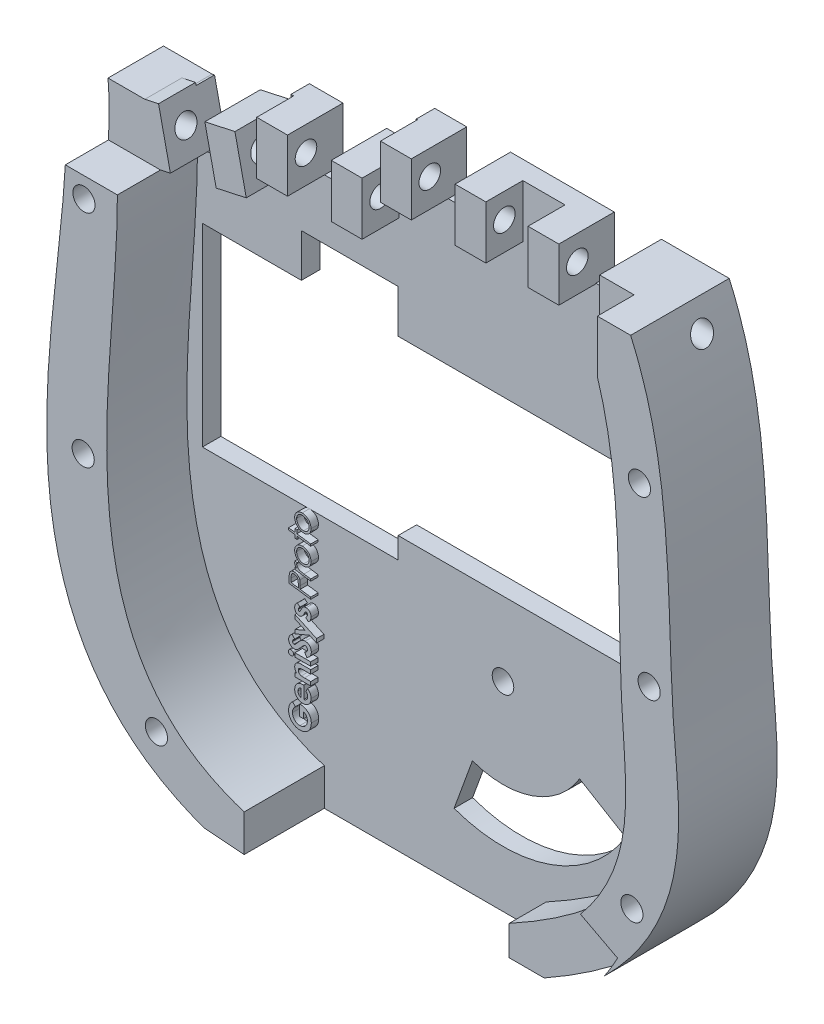
SolidWorks part; units mm, degrees
ref_plane "Front Plane" through (0, 0, 0) normal (0, 0, 1) x (1, 0, 0)
ref_plane "Top Plane" through (0, 0, 0) normal (0, 1, 0) x (1, 0, 0)
ref_plane "Right Plane" through (0, 0, 0) normal (1, 0, 0) x (0, 0, -1)
sketch "Sketch2" plane through (0, 0, 0) normal (0, 0, 1) x (1, 0, 0)
  line L0 (-18, 0) -> (18, 0)
  line L1 (-18, 0) -> (-18, 6)
  line L2 (18, 4.8369) -> (18, 0)
  line L3 (35.71, 104.3369) -> (-3.08, 104.3369)
  line L4 (-3.08, 104.3369) -> (-5.4197, 97.6369)
  line L5 (-5.4197, 97.6369) -> (-23.4197, 97.6369)
  line L6 (-23.4197, 97.6369) -> (-23.3737, 94.5493)
  line L7 (-23.3737, 94.5493) -> (-39.2, 91.09)
  spline S0 degree 3 poles (-18, 6) (-53.1212, 16.9957) (-35.2084, 66.9995) (-39.2, 91.09) knots 0 0 0 0 1 1 1 1
  spline S1 degree 3 poles (18, 4.8369) (37.3806, 15.4098) (45.3229, 29.9302) (41.68, 63.651) (44.3193, 88.8574) (35.71, 104.3369) knots 0 0 0 0 0.323626 0.459678 1 1 1 1
  dimension "D1" = 18
  dimension "D2" = 18
  dimension "D3" = 6
  dimension "D4" = 10.5
  dimension "D5" = 34.2
  dimension "D6" = 40.39
  dimension "D7" = 29.82
  dimension "D8" = 17.22
  dimension "D9" = 52.46
  dimension "D10" = 21.2
  dimension "D11" = 17.71
  dimension "D12" = 25.6263
  dimension "D13" = 25.26
  dimension "D14" = 38.79
  dimension "D15" = 109.25
  dimension "D16" = 6.7
  dimension "D17" = 18
  dimension "D18" = 16.2
extrude "Boss-Extrude1" add sketch "Sketch2" along normal blind 3
sketch "Sketch19" plane through (0, 0, 3) normal (0, 0, 1) x (1, 0, 0)
  line L0 (-3.953, 101.8369) -> (36.9908, 101.8369) construction
  line L1 (35.71, 104.3369) -> (-3.08, 104.3369) construction
  line L2 (16.315, 104.3369) -> (16.315, 82.7196) construction
  line L3 (-3.08, 104.3369) -> (-5.4197, 97.6369) construction
  line L4 (-5.0007, 98.8369) -> (38.0408, 98.8369) construction
  line L5 (-14.4197, 97.6369) -> (-14.4197, 19.4647) construction
  line L6 (-5.4197, 97.6369) -> (-23.4197, 97.6369) construction
  line L7 (32.86, 95.8369) -> (-25.0798, 95.8369) construction
  line L8 (-25.0798, 92.8369) -> (-5.4479, 92.8369) construction
  line L9 (-31.2868, 92.8197) -> (-30.2191, 87.935) construction
  line L10 (-30.2191, 87.935) -> (-26.5082, 88.7461) construction
  line L11 (-39.2, 91.09) -> (-23.3737, 94.5493) construction
  line L12 (-38.8717, 88.6027) -> (-23.0453, 92.0621) construction
  circle A16 centre (-18.9197, 77.8369) radius 1.6
  circle A17 centre (1.7305, 83.8369) radius 1.6
  circle A18 centre (23.11, 83.8369) radius 1.6
  circle A19 centre (22.9993, 31.1499) radius 1.6
  circle A20 centre (-32.5698, 65.7383) radius 1.6
  circle A21 centre (-32.5698, 43.2412) radius 1.6
  circle A22 centre (0, 14.3798) radius 1.6
  circle A23 centre (38.0408, 78.6285) radius 1.6
  circle A24 centre (38.0408, 56.4962) radius 1.6
  circle A25 centre (0.5343, 43.8548) radius 1.6
  circle A26 centre (-19.1897, 28.8836) radius 1.6
  spline S0 degree 3 poles (18, 4.8369) (37.3806, 15.4098) (45.3229, 29.9302) (41.68, 63.651) (44.3193, 88.8574) (35.71, 104.3369) knots 0 0 0 0 0.323626 0.459678 1 1 1 1 construction
  spline S1 degree 3 poles (-39.2, 91.09) (-35.2084, 66.9995) (-53.1212, 16.9957) (-18, 6) knots 0 0 0 0 1 1 1 1 construction
  dimension "D15" = 3.2
  dimension "D17" = 3.2
  dimension "D19" = 3.2
  dimension "D24" = 3.2
  dimension "D27" = 3.2
  dimension "D28" = 3.2
  dimension "D29" = 3.2
  dimension "D30" = 3.2
  dimension "D31" = 3.2
  dimension "D32" = 3.2
  dimension "D33" = 3.2
  dimension "D34" = 40
  dimension "D1" = 2.5
  dimension "D6" = 3
  dimension "D9" = 3
  dimension "D10" = 2.5
  dimension "D16" = 4.5
  dimension "D21" = 12
  dimension "D22" = 12
sketch "Sketch21" plane through (0, 0, 3) normal (0, 0, 1) x (1, 0, 0)
  line L0 (-19, 10) -> (-19, 40.6454) construction
  line L1 (-18, 6) -> (-18, 0) construction
  line L3 (-18, 0) -> (18, 0) construction
  text T0 "<b>GeniSys</b> <i>Proto</i>"
  dimension "D1" = 1
  dimension "D2" = 10
sketch "Sketch22" plane through (0, 0, 0) normal (0, 0, -1) x (-1, 0, 0)
  line L0 (-35.71, 104.3369) -> (-31.5125, 104.3369) construction
  line L1 (-26.06, 104.3369) -> (-21.06, 104.3369) construction
  line L2 (14.4197, 97.6369) -> (14.4197, 88.3883) construction
  line L3 (5.4197, 97.6369) -> (23.4197, 97.6369) construction
  line L5 (23.3737, 94.5493) -> (39.2, 91.09) construction
  line L6 (31.3845, 92.7983) -> (30.9574, 90.8444)
  line L7 (28.1815, 78.1443) -> (23.2968, 79.212)
  line L8 (23.2968, 79.212) -> (24.0015, 82.4359)
  line L9 (26.4998, 93.866) -> (31.3845, 92.7983)
  line L11 (34.7549, 92.0616) -> (34.3279, 90.1077)
  line L13 (34.4827, 76.767) -> (35.1874, 79.9908)
  line L14 (-26.06, 89.3369) -> (-21.06, 89.3369)
  line L16 (-5.6675, 99.2369) -> (-5.6675, 95.7369) construction
  line L17 (17.9697, 82.6369) -> (22.9697, 82.6369)
  line L18 (10.8697, 97.6369) -> (5.8697, 97.6369)
  line L19 (10.8697, 92.5369) -> (10.8697, 89.0369)
  line L20 (10.8697, 82.6369) -> (5.8697, 82.6369)
  line L21 (5.8697, 97.6369) -> (5.8697, 95.6369)
  line L22 (17.9697, 97.6369) -> (22.9697, 97.6369)
  line L23 (22.9697, 97.6369) -> (22.9697, 95.6369)
  line L24 (17.9697, 97.6369) -> (17.9697, 95.6369)
  line L25 (-26.06, 104.3369) -> (-26.06, 102.3369)
  line L26 (-9.2175, 104.3369) -> (-14.2175, 104.3369)
  line L27 (-9.2175, 104.3369) -> (-9.2175, 102.3369)
  line L28 (-9.2175, 89.3369) -> (-14.2175, 89.3369)
  line L29 (-14.2175, 104.3369) -> (-14.2175, 102.3369)
  line L31 (-28.5125, 104.3369) -> (-28.5125, 102.3369)
  line L33 (-31.5125, 104.3369) -> (-31.5125, 102.3369)
  line L34 (-21.06, 104.3369) -> (-21.06, 102.3369)
  line L35 (-26.06, 104.3369) -> (-21.06, 104.3369)
  line L36 (-2.1175, 89.3369) -> (2.8825, 89.3369)
  line L37 (-2.1175, 104.3369) -> (-2.1175, 102.3369)
  line L38 (2.8825, 104.3369) -> (2.8825, 102.3369)
  line L39 (-2.1175, 104.3369) -> (2.8825, 104.3369)
  line L45 (30.2955, 87.8159) -> (25.4108, 88.8836)
  line L46 (29.5481, 84.3967) -> (24.6634, 85.4643)
  line L47 (28.8861, 81.3682) -> (24.0015, 82.4359)
  line L48 (30.9574, 90.8444) -> (26.0728, 91.9121)
  line L49 (33.6659, 87.0792) -> (32.9185, 83.66)
  line L50 (37.2587, 89.4671) -> (37.6858, 91.421)
  line L51 (32.2566, 80.6315) -> (31.5519, 77.4076)
  line L52 (35.8493, 83.0193) -> (36.5967, 86.4386)
  line L53 (26.0728, 91.9121) -> (26.4998, 93.866)
  line L54 (30.2955, 87.8159) -> (29.5481, 84.3967)
  line L55 (28.8861, 81.3682) -> (28.1815, 78.1443)
  line L56 (24.6634, 85.4643) -> (25.4108, 88.8836)
  line L57 (2.8825, 102.3369) -> (-2.1175, 102.3369)
  line L58 (2.8825, 99.2369) -> (-2.1175, 99.2369)
  line L59 (2.8825, 95.7369) -> (-2.1175, 95.7369)
  line L60 (2.8825, 92.6369) -> (-2.1175, 92.6369)
  line L61 (2.8825, 99.2369) -> (2.8825, 95.7369)
  line L62 (-2.1175, 99.2369) -> (-2.1175, 95.7369)
  line L63 (-9.2175, 99.2369) -> (-9.2175, 95.7369)
  line L64 (-14.2175, 99.2369) -> (-14.2175, 95.7369)
  line L66 (-21.06, 99.2369) -> (-21.06, 95.7369)
  line L67 (-26.06, 99.2369) -> (-26.06, 95.7369)
  line L68 (-28.5125, 99.2369) -> (-28.5125, 95.7369)
  line L69 (-31.5125, 99.2369) -> (-31.5125, 95.7369)
  line L70 (2.8825, 92.6369) -> (2.8825, 89.3369)
  line L71 (-2.1175, 92.6369) -> (-2.1175, 89.3369)
  line L72 (-5.6675, 92.6369) -> (-5.6675, 85.3883) construction
  line L73 (-9.2175, 92.6369) -> (-9.2175, 89.3369)
  line L74 (-14.2175, 92.6369) -> (-14.2175, 89.3369)
  line L75 (-21.06, 92.6369) -> (-21.06, 89.3369)
  line L76 (-26.06, 92.6369) -> (-26.06, 89.3369)
  line L78 (-28.5125, 92.6369) -> (-28.5125, 89.3369)
  line L79 (-31.5125, 92.6369) -> (-31.5125, 89.3369)
  line L80 (-2.1175, 104.3369) -> (3.08, 104.3369) construction
  line L81 (-9.2175, 102.3369) -> (-14.2175, 102.3369)
  line L82 (-9.2175, 99.2369) -> (-14.2175, 99.2369)
  line L83 (-9.2175, 95.7369) -> (-14.2175, 95.7369)
  line L84 (-9.2175, 92.6369) -> (-14.2175, 92.6369)
  line L85 (-14.2175, 104.3369) -> (-9.2175, 104.3369) construction
  line L86 (-21.06, 102.3369) -> (-26.06, 102.3369)
  line L87 (-21.06, 99.2369) -> (-26.06, 99.2369)
  line L88 (-21.06, 95.7369) -> (-26.06, 95.7369)
  line L89 (-21.06, 92.6369) -> (-26.06, 92.6369)
  line L93 (22.9697, 95.6369) -> (17.9697, 95.6369)
  line L94 (22.9697, 92.5369) -> (17.9697, 92.5369)
  line L95 (22.9697, 89.0369) -> (17.9697, 89.0369)
  line L96 (22.9697, 85.9369) -> (17.9697, 85.9369)
  line L97 (37.2587, 89.4671) -> (36.5967, 86.4386)
  line L98 (5.4197, 97.6369) -> (23.4197, 97.6369) construction
  line L99 (10.8697, 95.6369) -> (5.8697, 95.6369)
  line L100 (10.8697, 92.5369) -> (5.8697, 92.5369)
  line L101 (10.8697, 89.0369) -> (5.8697, 89.0369)
  line L102 (10.8697, 85.9369) -> (5.8697, 85.9369)
  line L103 (22.9697, 92.5369) -> (22.9697, 89.0369)
  line L104 (17.9697, 92.5369) -> (17.9697, 89.0369)
  line L105 (5.8697, 92.5369) -> (5.8697, 89.0369)
  line L106 (5.8697, 85.9369) -> (5.8697, 82.6369)
  line L107 (10.8697, 85.9369) -> (10.8697, 82.6369)
  line L108 (17.9697, 85.9369) -> (17.9697, 82.6369)
  line L109 (22.9697, 85.9369) -> (22.9697, 82.6369)
  line L110 (10.8697, 95.6369) -> (10.8697, 97.6369)
  line L111 (34.3279, 90.1077) -> (33.6659, 87.0792)
  line L112 (30.9574, 90.8444) -> (30.2955, 87.8159)
  line L113 (26.1323, 92.1846) -> (25.4108, 88.8836)
  line L114 (22.9697, 95.6369) -> (22.9697, 92.5369)
  line L115 (17.9697, 95.6369) -> (17.9697, 92.5369)
  line L116 (10.8697, 95.6369) -> (10.8697, 92.5369)
  line L117 (5.8697, 95.6369) -> (5.8697, 92.5369)
  line L118 (2.8825, 102.3369) -> (2.8825, 99.2369)
  line L119 (-2.1175, 102.3369) -> (-2.1175, 99.2369)
  line L120 (-9.2175, 102.3369) -> (-9.2175, 99.2369)
  line L121 (-14.2175, 102.3369) -> (-14.2175, 99.2369)
  line L122 (-21.06, 102.3369) -> (-21.06, 99.2369)
  line L123 (-26.06, 102.3369) -> (-26.06, 99.2369)
  line L124 (-28.5125, 102.3369) -> (-28.5125, 99.2369)
  line L125 (-31.5125, 102.3369) -> (-31.5125, 99.2369)
  line M20 (39.2, 91.09) -> (23.3737, 94.5493)
  line M22 (23.4197, 97.6369) -> (5.4197, 97.6369)
  line M24 (3.08, 104.3369) -> (-35.71, 104.3369)
  dimension "D1" = 5
  dimension "D2" = 15
  dimension "D3" = 8
  dimension "D4" = 5
  dimension "D5" = 15
  dimension "D6" = 3.55
  dimension "D7" = 15
  dimension "D8" = 15
  dimension "D9" = 5
  dimension "D10" = 3
  dimension "D11" = 9.65
  dimension "D12" = 3.55
  dimension "D13" = 5
  dimension "D18" = 3.1
  dimension "D19" = 3.5
  dimension "D20" = 3.1
  dimension "D21" = 2
  dimension "D22" = 3.1
  dimension "D23" = 3.5
  dimension "D24" = 3.1
extrude "Finger Attachments" add sketch "Sketch22" against normal blind 9 contours L53 L48 L6 M20 | L68 L69 | L111 L97 | L125 L124 | L93 L23 L24 M22 | L94 L104 L95 L103 | L93 L115 L94 L114 | L48 L113 L45 L112 | L99 L110 L21 M22 | L99 L117 L100 L116 | L100 L105 L101 L19 | L57 L38 L37 M24 | L57 L119 L58 L118 | L58 L62 L59 L61 | L81 L27 L29 M24 | L81 L121 L82 L120 | L83 L63 L82 L64 | L86 L34 L25 M24 | L86 L123 L87 L122 | L88 L66 L87 L67 | L54 L46 L56 L45 | L48 L53 L9 L6 region at (-28.7286, 92.3552, 0) region at (-28.1841, 89.864, 0) region at (-8.3697, 96.6369, 0) region at (-20.4697, 96.6369, 0) region at (-8.3697, 94.0869, 0) region at (-8.3697, 90.7869, 0) region at (-20.4697, 94.0869, 0) region at (-20.4697, 90.7869, 0) region at (23.56, 103.3369, 0) region at (-0.3825, 103.3369, 0) region at (11.7175, 103.3369, 0) region at (23.56, 100.7869, 0) region at (23.56, 97.4869, 0) region at (11.7175, 100.7869, 0) region at (11.7175, 97.4869, 0) region at (-0.3825, 100.7869, 0) region at (-0.3825, 97.4869, 0)
sketch "Sketch24" plane through (0, 0, 3) normal (0, 0, 1) x (1, 0, 0)
  line L0 (35.71, 104.3369) -> (44.71, 104.3369)
  line L4 (26.06, 104.3369) -> (26.06, 95.7369)
  line L5 (26.06, 104.3369) -> (26.06, 95.7369)
  line L6 (-18, 6) -> (-18, 0)
  line L7 (21.06, 95.7369) -> (21.06, 104.3369)
  line L8 (21.06, 95.7369) -> (21.06, 104.3369)
  line L9 (26.06, 95.7369) -> (21.06, 95.7369)
  line L10 (18, 4.8369) -> (18, 0)
  line L11 (26.06, 95.7369) -> (21.06, 95.7369)
  line L12 (-18, 6) -> (-18, 0)
  line L13 (-18, 0) -> (18, 0)
  line L42 (18, 0) -> (18, 4.8369)
  line L43 (35.71, 104.3369) -> (26.06, 104.3369)
  line L44 (35.71, 104.3369) -> (26.06, 104.3369)
  line L45 (-3.08, 104.3369) -> (-5.4197, 97.6369)
  line L46 (-3.08, 104.3369) -> (-5.4197, 97.6369)
  line L47 (-5.4197, 97.6369) -> (-5.8697, 97.6369)
  line L48 (-5.4197, 97.6369) -> (-5.8697, 97.6369)
  line L49 (-23.4197, 97.6369) -> (-23.3737, 94.5493)
  line L50 (-23.4197, 97.6369) -> (-23.3737, 94.5493)
  line L51 (-23.3737, 94.5493) -> (-26.4998, 93.866)
  line L52 (-23.3737, 94.5493) -> (-26.4998, 93.866)
  line L53 (-22.9697, 89.0369) -> (-22.9697, 97.6369)
  line L54 (-22.9697, 89.0369) -> (-22.9697, 97.6369)
  line L55 (-22.9697, 97.6369) -> (-23.4197, 97.6369)
  line L56 (-22.9697, 97.6369) -> (-23.4197, 97.6369)
  line L57 (-29.5481, 84.3967) -> (-31.3845, 92.7983)
  line L58 (-29.5481, 84.3967) -> (-31.3845, 92.7983)
  line L59 (-31.3845, 92.7983) -> (-39.2, 91.09)
  line L60 (21.06, 104.3369) -> (14.2175, 104.3369)
  line L61 (21.06, 104.3369) -> (14.2175, 104.3369)
  line L62 (14.2175, 104.3369) -> (14.2175, 95.7369)
  line L63 (14.2175, 104.3369) -> (14.2175, 95.7369)
  line L64 (9.2175, 95.7369) -> (9.2175, 104.3369)
  line L65 (9.2175, 95.7369) -> (9.2175, 104.3369)
  line L66 (9.2175, 104.3369) -> (2.1175, 104.3369)
  line L67 (9.2175, 104.3369) -> (2.1175, 104.3369)
  line L68 (2.1175, 104.3369) -> (2.1175, 95.7369)
  line L69 (2.1175, 104.3369) -> (2.1175, 95.7369)
  line L70 (-2.8825, 95.7369) -> (-2.8825, 104.3369)
  line L71 (-2.8825, 95.7369) -> (-2.8825, 104.3369)
  line L72 (-2.8825, 104.3369) -> (-3.08, 104.3369)
  line L73 (-2.8825, 104.3369) -> (-3.08, 104.3369)
  line L74 (-5.8697, 97.6369) -> (-5.8697, 89.0369)
  line L75 (-5.8697, 97.6369) -> (-5.8697, 89.0369)
  line L76 (-10.8697, 89.0369) -> (-10.8697, 97.6369)
  line L77 (-10.8697, 89.0369) -> (-10.8697, 97.6369)
  line L78 (-10.8697, 97.6369) -> (-17.9697, 97.6369)
  line L79 (-10.8697, 97.6369) -> (-17.9697, 97.6369)
  line L80 (-17.9697, 97.6369) -> (-17.9697, 89.0369)
  line L81 (-17.9697, 97.6369) -> (-17.9697, 89.0369)
  line L82 (-26.4998, 93.866) -> (-24.6634, 85.4643)
  line L83 (-26.4998, 93.866) -> (-24.6634, 85.4643)
  line L84 (14.2175, 95.7369) -> (9.2175, 95.7369)
  line L85 (14.2175, 95.7369) -> (9.2175, 95.7369)
  line L86 (2.1175, 95.7369) -> (-2.8825, 95.7369)
  line L87 (2.1175, 95.7369) -> (-2.8825, 95.7369)
  line L88 (-5.8697, 89.0369) -> (-10.8697, 89.0369)
  line L89 (-5.8697, 89.0369) -> (-10.8697, 89.0369)
  line L90 (-17.9697, 89.0369) -> (-22.9697, 89.0369)
  line L91 (-17.9697, 89.0369) -> (-22.9697, 89.0369)
  line L92 (-24.6634, 85.4643) -> (-29.5481, 84.3967)
  line L93 (-24.6634, 85.4643) -> (-29.5481, 84.3967)
  line L146 (-39.2, 91.09) -> (-47.2, 91.09)
  line L147 (-47.2, 91.09) -> (-47.2, 91.9974)
  line L148 (-18, 0) -> (-24.4678, 0.4929)
  line L149 (18, 0) -> (23.6874, 0)
  line L150 (32.5502, 112.3626) -> (40.3879, 112.3626)
  spline S2 degree 3 poles (-2961.8078, -332.2212) (-163.8829, -81.2812) (51.7246, -29.3259) (31.6191, 156.7779) (150.9531, 334.6839) (-2802.2586, -849.4179) knots -1.757258 -1.757258 -1.757258 -1.757258 0.323626 0.459678 3.761705 3.761705 3.761705 3.761705 only from (18, 4.8369) to (35.71, 104.3369)
  spline S3 degree 3 poles (18, 4.8369) (37.3806, 15.4098) (45.3229, 29.9302) (41.68, 63.651) (44.3193, 88.8574) (35.71, 104.3369) knots 0 0 0 0 0.323626 0.459678 1 1 1 1
  spline S4 degree 3 poles (-2337.987, -1833.8607) (2351.9117, 2305.3454) (-2495.8331, -2099.3588) (2451.7998, 1700.8843) knots -2.84826 -2.84826 -2.84826 -2.84826 3.517723 3.517723 3.517723 3.517723 only from (-39.2, 91.09) to (-18, 6)
  spline S5 degree 3 poles (-39.2, 91.09) (-35.2084, 66.9995) (-53.1212, 16.9957) (-18, 6) knots 0 0 0 0 1 1 1 1
  spline S7 degree 3 poles (-47.2, 91.9974) (-47.1599, 91.6862) (-47.0914, 91.0758) (-46.9812, 89.745) (-46.9041, 87.9578) (-46.9027, 85.6162) (-47.0137, 82.2693) (-47.3399, 77.7113) (-47.9351, 71.7826) (-48.6252, 65.5104) (-49.5197, 56.8238) (-50.2972, 45.5886) (-49.787, 34.3505) (-47.9781, 25.6161) (-45.7185, 19.2851) (-42.3475, 13.3294) (-38.4814, 8.8916) (-34.7453, 5.7993) (-31.6335, 3.7363) (-28.7871, 2.2454) (-26.3709, 1.1975) (-25.1024, 0.717) (-24.4678, 0.4929) knots 0 0 0 0 0.015625 0.03125 0.0625 0.09375 0.125 0.1875 0.25 0.3125 0.375 0.5 0.625 0.6875 0.75 0.8125 0.875 0.90625 0.9375 0.96875 0.984375 1 1 1 1
  spline S9 degree 3 poles (23.6874, 0) (24.1914, 0.2848) (25.2039, 0.8668) (27.1427, 2.0202) (29.4553, 3.4709) (32.0445, 5.2201) (35.2626, 7.5707) (38.8592, 10.5492) (42.5343, 14.2118) (45.5956, 17.9783) (48.8831, 23.1381) (51.5265, 29.7806) (52.6555, 37.689) (52.4444, 43.8229) (52.071, 48.3962) (51.7806, 51.6635) (51.5616, 54.8562) (51.3342, 59.2517) (51.1345, 64.8715) (50.8891, 71.7793) (50.488, 78.7784) (49.7699, 85.8145) (48.7611, 91.6626) (47.6112, 96.2996) (46.5517, 99.7458) (45.2691, 103.1479) (44.1215, 105.6536) (43.271, 107.3001) (42.903, 107.9801) (42.5981, 108.5249) (42.3696, 108.9222) (42.1787, 109.2535) (41.7775, 109.9501) (41.1839, 110.9806) (40.653, 111.9024) (40.3879, 112.3626) knots 0 0 0 0 0.00814 0.016279 0.032558 0.048837 0.065116 0.097674 0.130232 0.16279 0.195349 0.260465 0.325581 0.390697 0.423255 0.455813 0.488371 0.52093 0.586046 0.651162 0.716278 0.781394 0.846511 0.879069 0.911627 0.944185 0.976743 0.984882 0.993022 0.997092 1.001161 1.005231 1.009301 1.02558 1.041859 1.041859 1.041859 1.041859
  dimension "D3" = 9
  dimension "D2" = 8
  dimension "D1" = 0
extrude "Sides" add sketch "Sketch24" along normal blind 13 and the other way blind 3 contours S5 | S3 region at (40.21, 103.238, 3) region at (-40.646, 42.3902, 3)
sketch "Sketch25" plane through (0, 0, 3) normal (0, 0, 1) x (1, 0, 0)
  line L0 (24, 30) -> (62.7669, 72.4354)
  line L2 (24, 30) -> (23.5361, 28.0545)
  line L3 (24, 30) -> (25.8473, 30.7664)
  line L4 (24, 30) -> (26, 30)
  line L5 (18, 4.8369) -> (18, 0) construction
  line L6 (24, 30) -> (18, 4.8369)
  line L8 (18, 4.8369) -> (58.2084, 4.8369)
  line L9 (58.2084, 4.8369) -> (58.2084, 30.7664)
  line L10 (25.9869, 29.7713) -> (24, 30)
  line L11 (58.2084, 30.7664) -> (24, 30)
  circle A0 centre (24, 30) radius 2
  dimension "D1" = 4
  dimension "D2" = 6
sketch "Sketch26" plane through (0, 0, 3) normal (0, 0, 1) x (1, 0, 0)
  line L0 (35.71, 104.3369) -> (26.06, 104.3369) construction
  line L1 (3.6799, 12.2251) -> (3.0651, 10.536)
  line L2 (11, 32.3369) -> (30.8863, 20.388)
  line L3 (11, 32.3369) -> (12.75, 32.3369)
  line L4 (11, 32.3369) -> (10.4015, 30.6925)
  line L6 (6.0407, 18.7114) -> (3.6799, 12.2251)
  line L7 (18, 0) -> (18, 4.8369) construction
  circle A0 centre (11, 32.3369) radius 1.75
  arc A1 (6.0407, 18.7114) -> (23.4289, 24.8689) centre (11, 32.3369) ccw
  arc A2 (3.0651, 10.536) -> (30.8863, 20.388) centre (11, 32.3369) ccw
  dimension "D4" = 14.5
  dimension "D5" = 23.2
  dimension "D6" = 3.5
  dimension "D1" = 7
  dimension "D2" = 72
  dimension "D3" = 110
  dimension "D7" = 79
extrude "Thumb Cuts" cut sketch "Sketch26" against normal blind 10 contours L3 A0 L4 | L4 A0 L3 | L1 A2 A1 L6 | L4 A0 L2 region at (16.9086, 15.6515, 3) region at (11.3593, 31.3222, 3) region at (12.1106, 32.0289, 3) region at (10.7487, 32.6957, 3)
sketch "Sketch30" plane through (-17.9697, 0, 0) normal (1, 0, 0) x (0, 0, -1)
  line L0 (-9, 97.6369) -> (-3, 97.6369) construction
  line L1 (-9, 97.6369) -> (-9, 89.0369) construction
  circle A0 centre (-6, 93.6369) radius 1.75
  dimension "D2" = 3.5
  dimension "D1" = 3
  dimension "D3" = 4
extrude "Ring Hole" cut sketch "Sketch30" against normal up to surface and the other way up to surface up to face at (-22.9697, 93.3369, 6) other way up to face at (-5.8697, 93.3369, 6)
sketch "Sketch31" plane through (-2.8825, 0, 0) normal (-1, 0, 0) x (0, 0, 1)
  line L0 (9, 104.3369) -> (9, 95.7369) construction
  line L1 (9, 104.3369) -> (3, 104.3369) construction
  circle A0 centre (6, 100.3369) radius 1.75
  dimension "D2" = 3.5
  dimension "D1" = 3
  dimension "D3" = 4
extrude "Dual Hole" cut sketch "Sketch31" against normal through all
extrude "Emboss" add sketch "Sketch21" along normal blind 1.2
sketch "Sketch34" plane through (0, 0, 3) normal (0, 0, 1) x (1, 0, 0)
  line L0 (39.3134, 95.8369) -> (39.3134, 104.3369)
  line L1 (35.71, 104.3369) -> (44.71, 104.3369) construction
  line L2 (39.3134, 104.3369) -> (31.885, 104.3369)
  line L3 (31.885, 104.3369) -> (39.3134, 95.8369)
  line L4 (-29.5481, 84.3967) -> (-39.2, 82.287)
  line L5 (-39.2, 82.287) -> (-41.1242, 91.09)
  line L6 (-39.2, 91.09) -> (-47.0975, 91.09) construction
  line L7 (-41.1242, 91.09) -> (-39.2, 91.5106)
  line L8 (-39.2, 91.5106) -> (-29.5481, 84.3967)
  spline S0 degree 3 poles (18, 4.8369) (37.3806, 15.4098) (45.3229, 29.9302) (41.68, 63.651) (44.3193, 88.8574) (35.71, 104.3369) knots 0 0 0 0 0.323626 0.459678 1 1 1 1 construction
extrude "AdjustCut" cut sketch "Sketch34" along normal up to surface (13 mm away) up to face at (-33.736, 55.3033, 16)
sketch "Sketch36" plane through (39.3134, 0, 0) normal (-1, 0, 0) x (0, 0, 1)
  line L1 (3, 104.3369) -> (10.034, 104.3369)
  line L2 (3, 104.3369) -> (3, 95.8369)
  line L3 (3, 95.8369) -> (10.034, 95.8369)
  line L5 (3, 104.3369) -> (10.034, 104.3369)
  line L6 (3, 104.3369) -> (3, 95.8369)
  line L7 (3, 95.8369) -> (10.034, 95.8369)
  line L8 (10.034, 104.3369) -> (10.034, 95.8369)
  circle A0 centre (6, 100.3369) radius 1.75
  line M2 (16, 104.3369) -> (3, 104.3369)
  line M3 (3, 104.3369) -> (3, 95.8369)
  line M4 (3, 95.8369) -> (16, 95.8369)
  circle M5 centre (6, 100.3369) radius 1.75
extrude "Boss-Extrude2" add sketch "Sketch36" along normal offset from surface (5.6034 mm away) 7.65 contours L8 M2 M3 M4 M5 region at (39.3134, 104.2266, 6.517) up to face at (26.06, 100.3369, 4.25)
sketch "Sketch37" plane through (0, 0, 3) normal (0, 0, 1) x (1, 0, 0)
  line L0 (-14.4197, 97.6369) -> (-14.4197, 59.4366) construction
  line L1 (5.6675, 104.3369) -> (5.6675, 58.4684) construction
  line L2 (9.2175, 104.3369) -> (2.1175, 104.3369) construction
  line L3 (29.885, 104.3369) -> (29.885, 51.3369) construction
  line L4 (33.71, 104.3369) -> (26.06, 104.3369) construction
  line L5 (-31.2868, 92.8197) -> (-41.0725, 90.8538) construction
  line L6 (-41.1242, 91.09) -> (-39.2, 82.287) construction
  line L7 (-36.1797, 91.8367) -> (-28.4923, 53.5704) construction
  line L8 (-25.6255, 70.7792) -> (-21.7197, 51.3369)
  line L9 (-37.7826, 72.3369) -> (36.985, 72.3369)
  line L10 (-37.7826, 72.3369) -> (-37.7826, 47.3369)
  line L11 (-21.7197, 51.3369) -> (-6.0197, 51.3369)
  line L12 (36.985, 72.3369) -> (36.985, 44.3369)
  line L13 (-37.7826, 68.3369) -> (-32.2679, 40.8854)
  line L14 (-2.8825, 104.3369) -> (-3.08, 104.3369) construction
  line L15 (-22.177, 40.8854) -> (-6.0197, 40.8854)
  line L16 (-37.7826, 68.3369) -> (-25.6255, 70.7792)
  line L17 (-37.7826, 47.3369) -> (-37.7826, 40.8854)
  line L18 (-37.7826, 40.8854) -> (-22.177, 40.8854)
  line L19 (-6.0197, 40.8854) -> (-6.0197, 44.3369)
  line L20 (23.285, 72.3369) -> (23.285, 51.3369)
  line L21 (-21.7197, 72.3369) -> (-6.0197, 72.3369)
  line L22 (-21.7197, 72.3369) -> (-21.7197, 51.3369)
  line L23 (-21.7197, 50.8405) -> (-21.627, 50.9289)
  line L24 (-6.0197, 72.3369) -> (-6.0197, 50.7305)
  line L25 (-0.9325, 72.3369) -> (12.2675, 72.3369)
  line L26 (-0.9325, 72.3369) -> (-0.9325, 44.3369)
  line L27 (-0.9325, 44.3369) -> (12.2675, 44.3369)
  line L28 (12.2675, 72.3369) -> (12.2675, 44.3369)
  line L29 (23.285, 51.3369) -> (23.285, 44.3369)
  line L30 (-21.7197, 72.3369) -> (-6.0197, 72.3369)
  line L31 (-21.7197, 72.3369) -> (-21.7197, 79.3369)
  line L32 (-21.7197, 79.3369) -> (-6.0197, 79.3369)
  line L33 (-6.0197, 72.3369) -> (-6.0197, 79.3369)
  line L34 (-21.7197, 50.8405) -> (-21.7197, 50.7305)
  line L35 (-6.0197, 44.3369) -> (36.985, 44.3369)
  line L36 (-25.6255, 70.7792) -> (-20.1107, 43.3276)
  line L37 (-32.2679, 40.8854) -> (-20.1107, 43.3276)
  dimension "D1" = 7.1
  dimension "D2" = 28
  dimension "D3" = 6.2
  dimension "D4" = 6.2
  dimension "D5" = 4
  dimension "D6" = 28
  dimension "D7" = 32
  dimension "D8" = 7.3
  dimension "D9" = 8.4
  dimension "D10" = 6.6
  dimension "D11" = 6.6
  dimension "D12" = 6.6
  dimension "D13" = 7
  dimension "D14" = 7
  dimension "D15" = 0
  dimension "D16" = 28
  dimension "D17" = 28
extrude "Cut-Extrude9" cut sketch "Sketch37" against normal blind 7.65 contours L20 L12 L9 | L28 L20 L9 | L28 L9 L26 L27 | L24 L26 L9 | L24 L9 L22 | L8 L22 L9 L10 L16 | L8 L16 L13 | L17 L18 L13 L10 | L18 | L9 L33 L32 L31 region at (-31.7562, 69.8173, 3) region at (-28.9467, 55.8323, 3) region at (-13.8697, 61.8369, 3) region at (-13.8697, 50.8929, 3) region at (-35.9444, 50.0359, 3) region at (-13.8697, 75.8369, 3) region at (5.6675, 58.3369, 3) region at (17.7762, 58.3369, 3) region at (30.135, 58.3369, 3)
hole_wizard "M3 Clearance Hole1" positions "Sketch38" profile "Sketch39" hole size "M3" standard "ANSI Metric" end condition through all
sketch "Sketch38" plane through (60.8706, 52.278, 16) normal (0, 0, 1) x (1, 0, 0)
  point P0 (-104.8732, 26.862)
  point P1 (-14.7294, 31.9842)
  point P2 (-13.1539, 4.198)
  point P3 (-15.9572, -28.4297)
  point P4 (-93.1113, -42.1412)
  point P5 (-104.998, -8.999)
sketch "Sketch39" plane through (-44.0026, 79.14, 16) normal (1, 0, 0) x (0, -1, 0)
  line L0 (0, 0) -> (0, 16)
  line L1 (0, 16) -> (1.8, 16)
  line L2 (1.8, 16) -> (1.8, 0)
  line L3 (1.8, 0) -> (0, 0)
  line L4 (0, -6.35) -> (0, 107.95) construction
  dimension "Thru Hole Dia." = 3.6
  dimension "Thru Hole Depth" = 16
sketch "Sketch40" plane through (-20.2465, -4.4255, 0) normal (0.9769, 0.2135, 0) x (0, 0, -1)
  line L1 (-16, 97.7705) -> (-3, 97.7705)
  line L2 (-16, 97.7705) -> (-16, 88.7597)
  line L3 (-16, 88.7597) -> (-3, 88.7597)
  line L4 (-3, 97.7705) -> (-3, 88.7597)
extrude "Boss-Extrude3" add sketch "Sketch40" along normal offset from surface (2.2798 mm away) 7.6 up to face at (-30.4663, 88.5975, 6)
sketch "Sketch41" plane through (-5.7099, -1.2481, 0) normal (0.9769, 0.2135, 0) x (0, 0, -1)
  line L1 (-9, 97.3597) -> (-3, 97.3597) construction
  circle A0 centre (-5.5, 93.3597) radius 1.75
  dimension "D2" = 3.5
  dimension "D3" = 4
sketch "Sketch42" plane through (0, 0, 16) normal (0, 0, 1) x (1, 0, 0)
  line L2 (-35.9457, 91.09) -> (-35.9457, 93.6024)
  line L3 (-36.9728, 82.7738) -> (-38.5786, 82.4228) construction
  line L4 (-38.5786, 82.4228) -> (-47.0313, 82.4228)
  line L5 (-35.9457, 93.6024) -> (-51.4275, 93.6024)
  line L7 (-47.0975, 91.09) -> (-46.8963, 91.0689)
  line L9 (-51.4275, 91.09) -> (-51.4275, 82.4228)
  line L10 (-51.4275, 82.4228) -> (-35.9457, 82.4228)
  line L11 (-35.9457, 82.4228) -> (-35.9457, 91.09)
  line L13 (-51.4275, 93.6024) -> (-51.4275, 91.09)
  spline S0 degree 3 poles (-38.5786, 82.4228) (-38.4693, 56.6147) (-49.3131, 15.8035) (-18, 6) knots 0.108425 0.108425 0.108425 0.108425 1 1 1 1 construction
  spline S1 degree 3 poles (-47.0975, 91.09) (-47.0966, 91.0807) (-47.0647, 90.7529) (-46.9812, 89.745) (-46.9041, 87.9578) (-46.9027, 85.6162) (-47.0137, 82.2693) (-47.3399, 77.7113) (-47.9351, 71.7826) (-48.6252, 65.5104) (-49.5197, 56.8238) (-50.2972, 45.5886) (-49.787, 34.3505) (-47.9781, 25.6161) (-45.7185, 19.2851) (-42.3475, 13.3294) (-38.4814, 8.8916) (-34.7453, 5.7993) (-31.6335, 3.7363) (-28.7871, 2.2454) (-26.3709, 1.1975) (-25.1024, 0.717) (-24.4678, 0.4929) knots 0.015169 0.015169 0.015169 0.015169 0.015625 0.03125 0.0625 0.09375 0.125 0.1875 0.25 0.3125 0.375 0.5 0.625 0.6875 0.75 0.8125 0.875 0.90625 0.9375 0.96875 0.984375 1 1 1 1 construction
  line M2 (-38.5786, 82.4228) -> (-36.9728, 82.7738)
  line M3 (-36.9728, 82.7738) -> (-38.897, 91.5768)
  line M4 (-38.897, 91.5768) -> (-41.1242, 91.09)
  line M5 (-41.1242, 91.09) -> (-47.0975, 91.09)
  spline M6 degree 3 poles (-47.2, 91.9974) (-47.1599, 91.6862) (-47.0914, 91.0758) (-46.9812, 89.745) (-46.9041, 87.9578) (-46.9027, 85.6162) (-47.0137, 82.2693) (-47.3399, 77.7113) (-47.9351, 71.7826) (-48.6252, 65.5104) (-49.5197, 56.8238) (-50.2972, 45.5886) (-49.787, 34.3505) (-47.9781, 25.6161) (-45.7185, 19.2851) (-42.3475, 13.3294) (-38.4814, 8.8916) (-34.7453, 5.7993) (-31.6335, 3.7363) (-28.7871, 2.2454) (-26.3709, 1.1975) (-25.1024, 0.717) (-24.4678, 0.4929) knots 0 0 0 0 0.015625 0.03125 0.0625 0.09375 0.125 0.1875 0.25 0.3125 0.375 0.5 0.625 0.6875 0.75 0.8125 0.875 0.90625 0.9375 0.96875 0.984375 1 1 1 1 only from (-47.0975, 91.09) to (-24.4678, 0.4929)
extrude "Cut-Extrude13" cut sketch "Sketch42" against normal blind 7 contours L5 L13 L9 L10 L11 L2 M6 M5 M4 M3 M2 | L4 M2 M3 M4 M5 M6 region at (-43.6866, 88.0126, 16)
sketch "Sketch43" plane through (0, 0, 16) normal (0, 0, 1) x (1, 0, 0)
  line L0 (11, 32.3369) -> (3.048, -2.4549)
  line L1 (11, 32.3369) -> (42.598, 15.7456)
  arc A0 (3.048, -2.4549) -> (42.598, 15.7456) centre (11, 32.3369) ccw
  arc A1 (5.1529, 6.7543) -> (34.2341, 20.1372) centre (11, 32.3369) ccw
  spline M6 degree 3 poles (35.71, 104.3369) (44.3193, 88.8574) (41.68, 63.651) (45.3229, 29.9302) (37.3806, 15.4098) (18, 4.8369) knots 0 0 0 0 0.540322 0.676374 1 1 1 1 only from (39.3134, 95.8369) to (18, 4.8369)
  line M7 (18, 4.8369) -> (18, 0)
  line M8 (18, 0) -> (23.6874, 0)
  spline M9 degree 3 poles (23.6874, 0) (24.1914, 0.2848) (25.2039, 0.8668) (27.1427, 2.0202) (29.4553, 3.4709) (32.0445, 5.2201) (35.2626, 7.5707) (38.8592, 10.5492) (42.5343, 14.2118) (45.5956, 17.9783) (48.8831, 23.1381) (51.5265, 29.7806) (52.6555, 37.689) (52.4444, 43.8229) (52.071, 48.3962) (51.7806, 51.6635) (51.5616, 54.8562) (51.3342, 59.2517) (51.1345, 64.8715) (50.8891, 71.7793) (50.488, 78.7784) (49.7699, 85.8145) (48.7611, 91.6626) (47.6112, 96.2996) (46.5517, 99.7458) (45.2691, 103.1479) (44.1215, 105.6536) (43.271, 107.3001) (42.903, 107.9801) (42.5981, 108.5249) (42.3696, 108.9222) (42.1787, 109.2535) (41.7775, 109.9501) (41.1839, 110.9806) (40.653, 111.9024) (40.3879, 112.3626) knots 0 0 0 0 0.00814 0.016279 0.032558 0.048837 0.065116 0.097674 0.130232 0.16279 0.195349 0.260465 0.325581 0.390697 0.423255 0.455813 0.488371 0.52093 0.586046 0.651162 0.716278 0.781394 0.846511 0.879069 0.911627 0.944185 0.976743 0.984882 0.993022 0.997092 1.001161 1.005231 1.009301 1.02558 1.041859 1.041859 1.041859 1.041859 only from (23.6874, 0) to (44.71, 104.3369)
extrude "Cut-Extrude15" cut sketch "Sketch43" against normal blind 7 contours A0 L1 M9 M6 M7 M8 | A1 L0 A0 L1 M9 M8 M7 M6 region at (23.1298, 5.9787, 16)
sketch "Sketch44" plane through (0, 0, 3) normal (0, 0, 1) x (1, 0, 0)
  line L0 (-36.9728, 82.7738) -> (-29.5481, 84.3967)
  line L1 (-17.9697, 97.6369) -> (-10.8697, 97.6369)
  line L2 (-17.9697, 97.6369) -> (-17.9697, 89.0369)
  line L3 (-17.9697, 89.0369) -> (-10.8697, 89.0369)
  line L4 (-10.8697, 97.6369) -> (-10.8697, 89.0369)
  line L5 (2.1175, 104.3369) -> (9.2175, 104.3369)
  line L6 (2.1175, 104.3369) -> (2.1175, 95.7369)
  line L7 (2.1175, 95.7369) -> (9.2175, 95.7369)
  line L8 (9.2175, 104.3369) -> (9.2175, 95.7369)
  line L9 (26.06, 104.3369) -> (33.71, 104.3369)
  line L10 (26.06, 104.3369) -> (26.06, 95.8369)
  line L11 (26.06, 95.8369) -> (33.71, 95.8369)
  line L12 (33.71, 104.3369) -> (33.71, 95.8369)
  line L13 (-36.9728, 82.7738) -> (-38.8092, 91.1754)
  line L14 (-29.5481, 84.3967) -> (-31.3845, 92.7983)
  line L15 (-38.8092, 91.1754) -> (-31.3845, 92.7983)
extrude "Cut-Extrude16" cut sketch "Sketch44" against normal through all both and the other way through all
extrude "Cut-Extrude17" cut sketch "Sketch41" against normal through all
sketch "Sketch45" plane through (26.06, 0, 0) normal (1, 0, 0) x (0, 0, -1)
  line L0 (-9, 95.7369) -> (-3, 95.8369)
  line L1 (-3, 95.8369) -> (-3, 93.8369)
  line L2 (-3, 93.8369) -> (-9, 95.7369)
  dimension "D1" = 2
